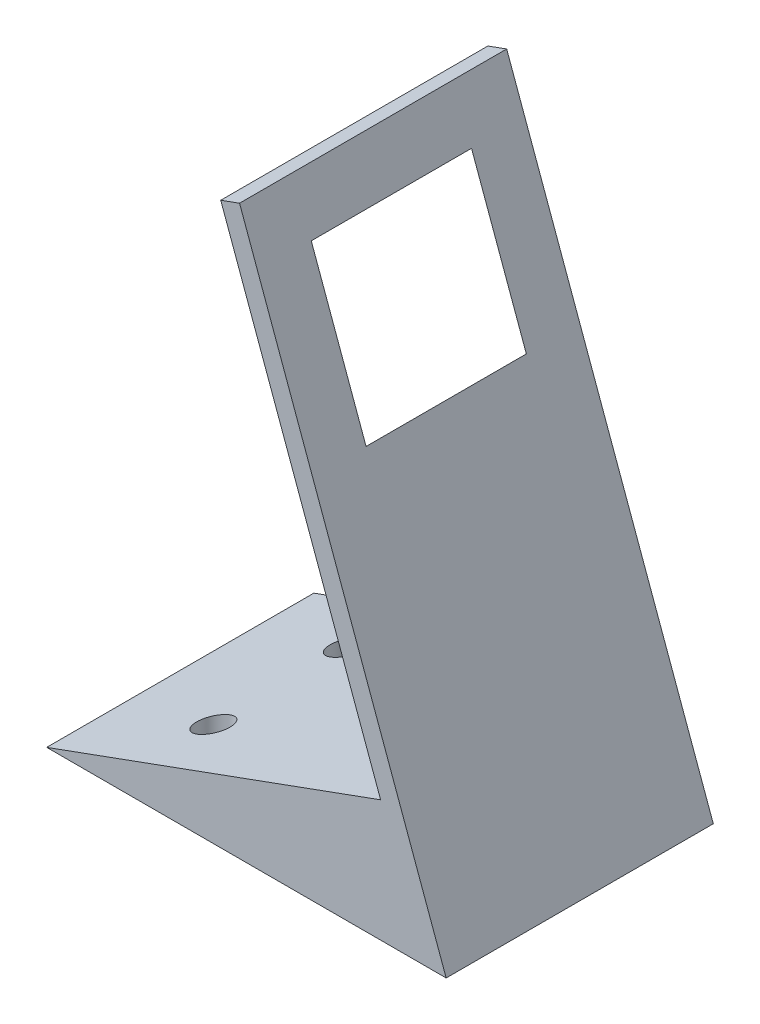
SolidWorks part; units mm, degrees
ref_plane "Front" through (0, 0, 0) normal (0, 0, 1) x (1, 0, 0)
ref_plane "Top" through (0, 0, 0) normal (0, 1, 0) x (1, 0, 0)
ref_plane "Right" through (0, 0, 0) normal (1, 0, 0) x (0, 0, -1)
sketch "Sketch1" plane through (0, 0, 0) normal (0, 0, 1) x (1, 0, 0)
  line L0 (0, 0) -> (50, 18.1985)
  line L1 (50, 18.1985) -> (26.0586, 83.977)
  line L2 (26.0586, 83.977) -> (28.8777, 85.0031)
  line L3 (28.8777, 85.0031) -> (60, -0.5048)
  line L4 (60, -0.5048) -> (60, 0)
  line L5 (60, 0) -> (0, 0)
  dimension "D1" = 20
  dimension "D2" = 60
  dimension "D3" = 3
  dimension "D4" = 70
  dimension "D5" = 50
extrude "Boss-Extrude1" add sketch "Sketch1" along normal blind 40 contours L5 L3 L2 L1 L0 region at (25.3555, 8.1225, 0)
sketch "Sketch2" plane through (0, 0, 0) normal (0, -1, 0) x (1, 0, 0)
  line L0 (0, 20) -> (29.9081, 20) construction
  line L1 (59.8162, 40) -> (0, 40) construction
  line L3 (29.9081, 40) -> (29.9081, 20) construction
  line L6 (0, 40) -> (0, 0) construction
  circle A0 centre (14.9541, 30) radius 1.5
  circle A1 centre (14.9541, 30) radius 2.5
  circle A2 centre (44.8622, 30) radius 1.5
  circle A3 centre (44.8622, 30) radius 2.5
  point P5 (0, 0)
  point P6 (29.9081, 40)
  point P8 (0, 0)
  point P9 (14.9541, 20)
  point P10 (0, 0)
  point P11 (29.9081, 30)
  dimension "D1" = 3
  dimension "D2" = 5
extrude "Cut-Extrude1" cut sketch "Sketch2" against normal up to next contours A0 | A2
extrude "Cut-Extrude3" cut sketch "Sketch2<4>" against normal up to next from offset 2 contours A1 A0 | A3 region at (12.5248, 0, 30) offset against normal yes
sketch "Sketch2<4>" plane through (0, 0, 0) normal (0, -1, 0) x (1, 0, 0) same geometry as "Sketch2"
ref_plane "Plane1" through (0, 0, 20) normal (0, 0, 1) x (1, 0, 0)
mirror "Mirror1" about plane through (0, 0, 20) normal (0, 0, 1) of "Cut-Extrude1", "Cut-Extrude3"
sketch "Sketch3" plane through (50, 18.1985, 0) normal (-0.9397, -0.342, 0) x (0, 0, 1)
  line L0 (0, 70) -> (0, 0) construction
  line L1 (5, 65) -> (35, 65)
  line L2 (5, 65) -> (5, 35)
  line L3 (5, 35) -> (35, 35)
  line L4 (35, 65) -> (35, 35)
  line L5 (40, 70) -> (40, 0) construction
  line L6 (40, 70) -> (0, 70) construction
  dimension "D1" = 5
  dimension "D2" = 5
  dimension "D3" = 5
  dimension "D4" = 30
sketch "Sketch4" plane through (52.8191, 19.2246, 0) normal (0.9397, 0.342, 0) x (0, 0, -1)
  line L4 (-5, 65) -> (-35, 65) construction
  line L5 (-35, 65) -> (-35, 35) construction
  line L6 (-5, 35) -> (-35, 35) construction
  line L7 (-5, 65) -> (-5, 35) construction
  line L8 (-5, 65) -> (-35, 65) construction
  line L9 (-35, 65) -> (-35, 35) construction
  line L10 (-5, 35) -> (-35, 35) construction
  line L11 (-5, 65) -> (-5, 35) construction
  line L12 (-8, 62) -> (-32, 62)
  line L13 (-32, 62) -> (-32, 38)
  line L14 (-8, 38) -> (-32, 38)
  line L15 (-8, 62) -> (-8, 38)
  dimension "D1" = 3
loft "Cut-Loft1" cut profiles "Sketch3", "Sketch4" connector at (27.7687, 79.2785, 35) connector at (31.6138, 77.4855, 32)
